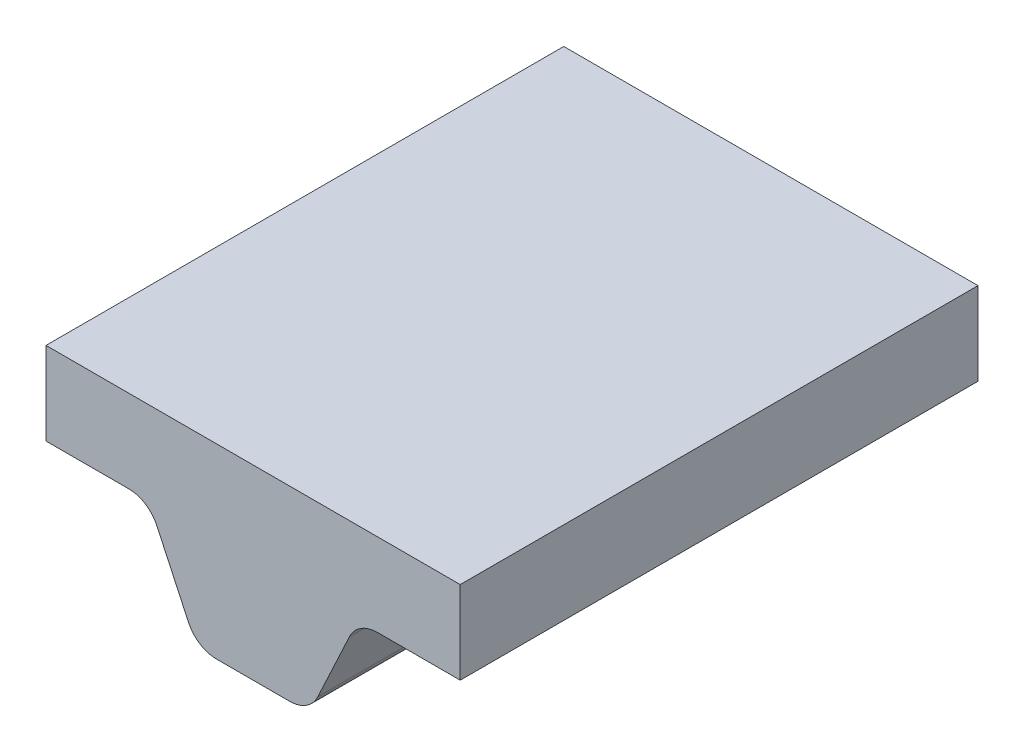
SolidWorks part; units mm, degrees
material "NEOPRENE"
ref_plane "Front Plane" through (0, 0, 0) normal (0, 0, 1) x (1, 0, 0)
ref_plane "Top Plane" through (0, 0, 0) normal (0, 1, 0) x (1, 0, 0)
ref_plane "Right Plane" through (0, 0, 0) normal (1, 0, 0) x (0, 0, -1)
ref_axis "X Axis" through (88.99, 0, 0) along (-1, 0, 0)
ref_axis "Y Axis" through (0, 55, 0) along (0, -1, 0)
ref_axis "Z Axis" through (0, 0, -88.99) along (0, 0, 1)
sketch "Sketch1" plane through (0, 0, 0) normal (0, 0, 1) x (1, 0, 0)
  line L1 (2.54, -0.508) -> (-2.54, -0.508) construction
  line L2 (2.54, -0.508) -> (2.54, 0.508)
  line L3 (2.54, 0.508) -> (-2.54, 0.508)
  line L4 (-2.54, -0.508) -> (-2.54, 0.508)
  line L5 (0, 0.508) -> (0, -0.508) construction
  line L6 (2.54, 0) -> (-2.54, 0) construction
  line L10 (0, -55) -> (0, 55) construction
  line L11 (-1.1804, -0.7274) -> (-0.7928, -1.5586)
  line L12 (-0.4484, -1.778) -> (0.4484, -1.778)
  line L13 (0.7928, -1.5586) -> (1.1804, -0.7274)
  line L14 (-1.5248, -0.508) -> (-2.54, -0.508)
  line L15 (1.5248, -0.508) -> (2.54, -0.508)
  arc A0 (1.1804, -0.7274) -> (1.5248, -0.508) centre (1.5248, -0.888) cw
  arc A1 (0.4484, -1.778) -> (0.7928, -1.5586) centre (0.4484, -1.398) ccw
  arc A2 (-0.7928, -1.5586) -> (-0.4484, -1.778) centre (-0.4484, -1.398) ccw
  arc A3 (-1.1804, -0.7274) -> (-1.5248, -0.508) centre (-1.5248, -0.888) ccw
  point P0 (0, 0)
  point P6 (1.2827, -0.508)
  point P21 (0, -1.778)
  point P23 (-1.2827, -0.508)
  dimension "D2" = 0.38
  dimension "D1" = 5.08
  dimension "D3" = 0.508
  dimension "D5" = 2.286
  dimension "D8" = 50
  dimension "D9" = 1.27
  dimension "D10" = 2.5654
  dimension "D11" = 1.2827
extrude "Boss-Extrude1" add sketch "Sketch1" along normal mid plane 6.35
